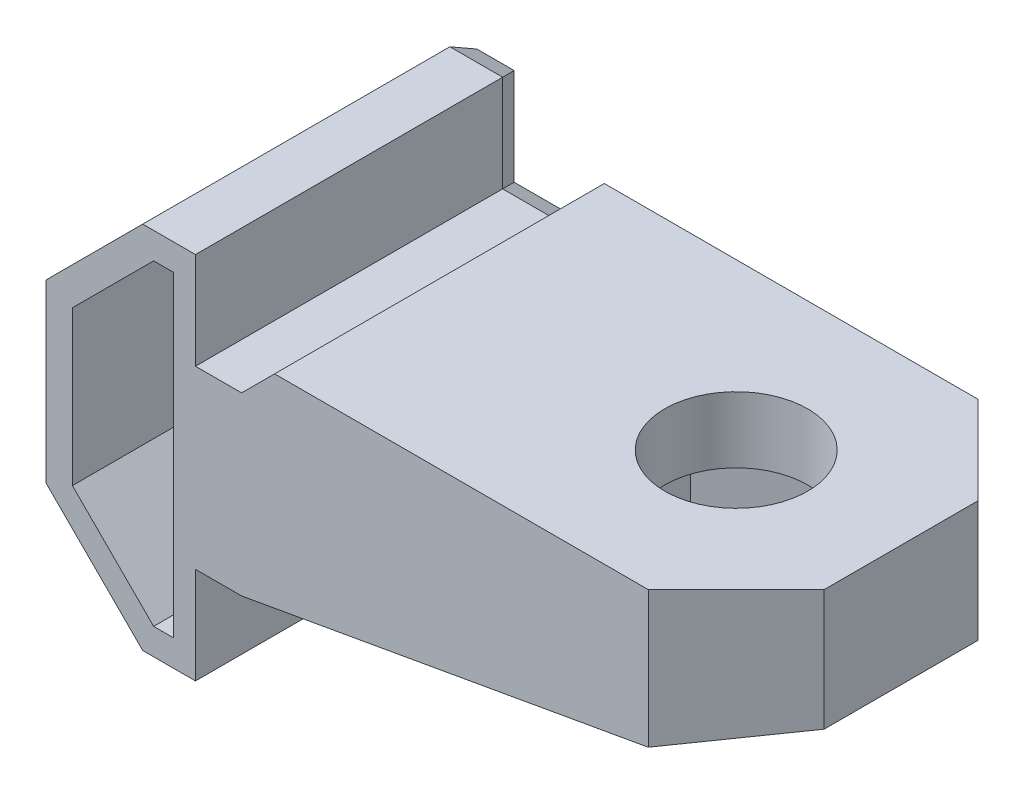
SolidWorks part; units mm, degrees
ref_plane "Alzado" through (0, 0, 0) normal (0, 0, 1) x (1, 0, 0)
ref_plane "Planta" through (0, 0, 0) normal (0, 1, 0) x (1, 0, 0)
ref_plane "Vista lateral" through (0, 0, 0) normal (1, 0, 0) x (0, 0, -1)
sketch "Croquis1" plane through (0, 0, 0) normal (0, 0, 1) x (1, 0, 0)
  line L0 (0, 0) -> (0, 5301.9663) construction
  line L1 (0, 0) -> (5301.9663, 0) construction
  line L2 (-4.8553, 4) -> (5297.111, 4) construction
  line L3 (0, 4) -> (-2.1, 4)
  line L4 (-8.9, 5.9678) -> (-8.9, -5295.9985) construction
  line L5 (-2.1, 7.8714) -> (-2.1, -5294.095) construction
  line L6 (-2.1, 4) -> (-2.1, 8.4)
  line L8 (-8.9, 4) -> (-8.9, -4)
  line L10 (-2.1, -4) -> (-2.1, -8.4)
  line L11 (0, -4) -> (-2.1, -4)
  line L12 (0, 4) -> (0, -4)
  line L13 (-4.5, -15.5102) -> (-4.5, 49984.4898) construction
  line L14 (-2.1, -8.4) -> (-4.5, -8.4)
  line L15 (-4.5, -8.4) -> (-8.9, -4)
  line L16 (-4.5, 8.4) -> (-8.9, 4)
  line L17 (-2.1, 8.4) -> (-4.5, 8.4)
  point P17 (-8.9, 0)
  dimension "D1" = 8
  dimension "D2" = 6.8
  dimension "D3" = 2.1
  dimension "D4" = 8
  dimension "D5" = 16.8
  dimension "D6" = 2.4
extrude "Saliente-Extruir1" add sketch "Croquis1" along normal mid plane 15
sketch "Croquis6" plane through (0, 0, -7.5) normal (0, 0, -1) x (-1, 0, 0)
  line L0 (0, 0) -> (-50000, 0) construction
  line L1 (0, 0) -> (0, 50000) construction
  line L2 (-15, 0) -> (-15, 50000) construction
  line L3 (-3.8361, 5.5) -> (-50003.8361, 5.5) construction
  line L4 (0, 4) -> (2.1, 4) construction
  line L5 (0, 4) -> (-1.5, 5.5)
  line L6 (-1.5, 5.5) -> (-22.5, 5.5)
  line L7 (-22.5, 5.5) -> (-22.5, 0)
  line L8 (-22.5, 0) -> (0, -4)
  line L9 (0, -4) -> (0, 4)
  dimension "D1" = 15
  dimension "D2" = 1.5
  dimension "D3" = 15
  dimension "D4" = 45
extrude "Saliente-Extruir2" add sketch "Croquis6" against normal through all
sketch "Croquis7" plane through (0, 5.5, 0) normal (0, 1, 0) x (1, 0, 0)
  line L0 (0, 0) -> (50000, 0) construction
  line L1 (15, 0) -> (15, 50000) construction
  line L2 (0, -7.5) -> (0, 7.5) construction
  circle A0 centre (15, 0) radius 3.25
  dimension "D2" = 6.5
  dimension "D1" = 15
extrude "Cortar-Extruir4" cut sketch "Croquis7" against normal through all
sketch "Croquis8" plane through (0, 5.5, 0) normal (0, 1, 0) x (1, 0, 0)
  line L1 (15, 5.658) -> (10.1, 2.829)
  line L2 (10.1, 2.829) -> (10.1, -2.829)
  line L3 (10.1, -2.829) -> (15, -5.658)
  line L4 (15, -5.658) -> (19.9, -2.829)
  line L5 (19.9, -2.829) -> (19.9, 2.829)
  line L6 (19.9, 2.829) -> (15, 5.658)
  circle A0 centre (15, 0) radius 4.9 construction
  dimension "D1" = 9.8
extrude "Cortar-Extruir5" cut sketch "Croquis8" against normal blind 10 from offset 3 offset against normal yes
sketch "Croquis9" plane through (0, 2.5, 0) normal (0, -1, 0) x (1, 0, 0)
  line L1 (10.1, 2.829) -> (7.7976, 2.829)
  line L2 (10.1, 2.829) -> (10.1, -2.829)
  line L3 (10.1, -2.829) -> (7.7976, -2.829)
  line L4 (7.7976, 2.829) -> (7.7976, -2.829)
  line L5 (10.1, 2.829) -> (7.7976, -2.829) construction
  line L6 (10.1, -2.829) -> (7.7976, 2.829) construction
  point P4 (8.9488, 0)
extrude "Saliente-Extruir3" add sketch "Croquis9" along normal blind 7
chamfer "Chaflán3" distance 2 angle 45 2 edges at (8.9488, -2.4091, 2.829) (8.9488, -2.4091, -2.829)
sketch "Croquis5" plane through (0, 0, 7.5) normal (0, 0, 1) x (1, 0, 0)
  line L0 (-3.1, 7.2) -> (-3.1, -7.2)
  line L3 (-7.7, -3.5029) -> (-7.7, 3.5029)
  line L4 (-7.7, 3.5029) -> (-4.0029, 7.2)
  line L5 (-4.0029, 7.2) -> (-3.1, 7.2)
  line L6 (0, 0) -> (-50000, 0) construction
  line L8 (-4.0029, -7.2) -> (-3.1, -7.2)
  line L9 (-7.7, -3.5029) -> (-4.0029, -7.2)
  line L10 (-2.1, 4) -> (-2.1, 8.4) construction
  line L11 (-2.1, 8.4) -> (-4.5, 8.4) construction
  line L12 (-4.5, 8.4) -> (-8.9, 4) construction
  line L13 (-8.9, 4) -> (-8.9, -4) construction
  dimension "D1" = 1
  dimension "D2" = 1.2
  dimension "D3" = 1.2
  dimension "D4" = 1.2
extrude "Cortar-Extruir3" cut sketch "Croquis5" against normal through all
chamfer "Chaflán4" distance 4 angle 45 2 edges at (22.5, 2.75, -7.5) (22.5, 2.75, 7.5)
chamfer "Chaflán2" distance 0.5 angle 64 9 edges at (-1.05, 4, -7.5) (-6.7, 6.2, -7.5) (-3.3, 8.4, -7.5) (-2.1, 6.2, -7.5) (-1.05, -4, -7.5) (-2.1, -6.2, -7.5) (-6.7, -6.2, -7.5) (-3.3, -8.4, -7.5) (-8.9, 0, -7.5) first distance on face at (-4.9343, 0, -7.5)
